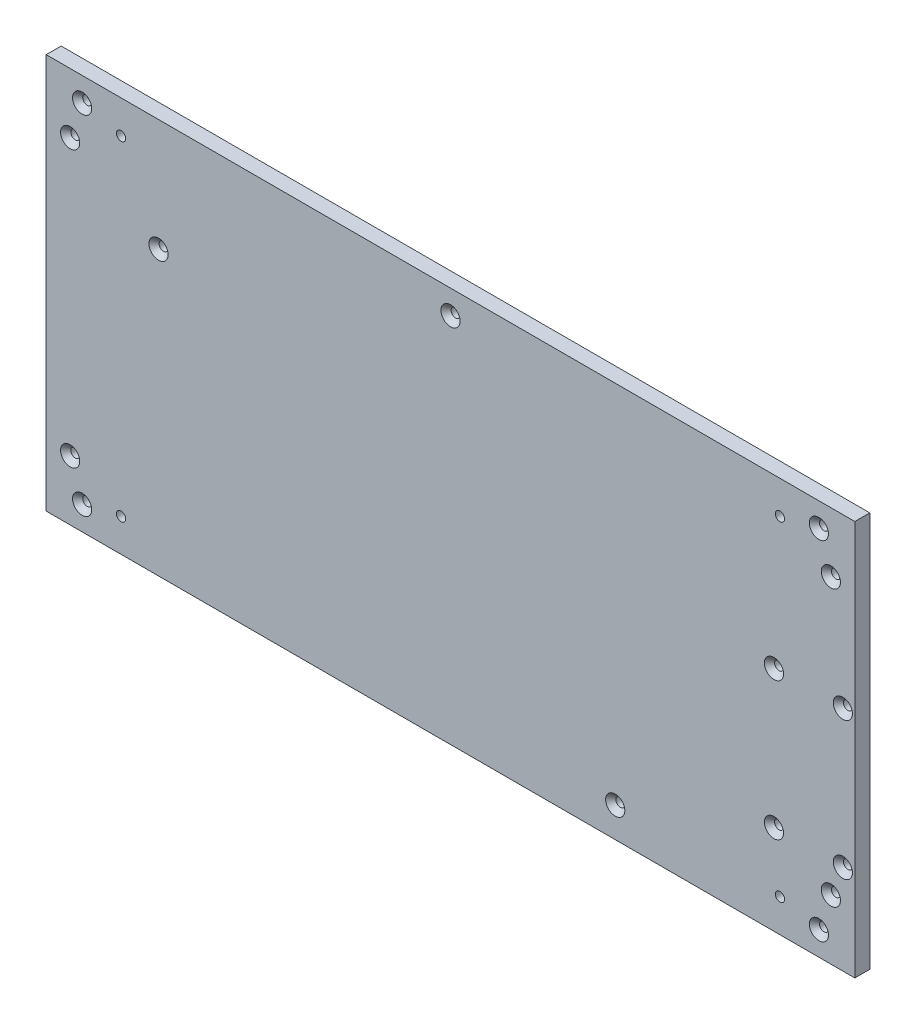
SolidWorks part; units mm, degrees
ref_plane "Front Plane" through (0, 0, 0) normal (0, 0, 1) x (1, 0, 0)
ref_plane "Top Plane" through (0, 0, 0) normal (0, 1, 0) x (1, 0, 0)
ref_plane "Right Plane" through (0, 0, 0) normal (1, 0, 0) x (0, 0, -1)
sketch "Sketch1" plane through (0, 0, 0) normal (0, 0, 1) x (1, 0, 0)
  line L1 (135, -66) -> (-135, -66)
  line L2 (135, -66) -> (135, 66)
  line L3 (135, 66) -> (-135, 66)
  line L4 (-135, -66) -> (-135, 66)
  line L5 (135, -66) -> (-135, 66) construction
  line L6 (135, 66) -> (-135, -66) construction
  point P0 (0, 0)
  dimension "D1" = 270
  dimension "D2" = 132
extrude "Base" add sketch "Sketch1" along normal mid plane 5 contours L4 L1 L2 L3 region at (0, 0, 0)
sketch "Sketch2" plane through (0, 0, 2.5) normal (0, 0, 1) x (1, 0, 0)
  line L0 (135, 66) -> (-135, 66) construction
  line L1 (135, -66) -> (135, 66) construction
  line L2 (-135, -66) -> (-135, 66) construction
  line L3 (135, -66) -> (-135, -66) construction
  circle A0 centre (-127, -46) radius 1.5
  circle A1 centre (-123, -58) radius 1.5
  circle A2 centre (-127, 46) radius 1.5
  circle A3 centre (-123, 58) radius 1.5
  circle A5 centre (0, 58) radius 1.5
  circle A6 centre (123, -58) radius 1.5
  circle A7 centre (127, -46) radius 1.5
  circle A8 centre (127, 46) radius 1.5
  circle A9 centre (123, 58) radius 1.5
  dimension "D5" = 8
  dimension "D10" = 3
  dimension "D2" = 8
  dimension "D3" = 12
  dimension "D4" = 12
  dimension "D6" = 20
  dimension "D7" = 20
  dimension "D8" = 8
  dimension "D9" = 8
extrude "FastenersHoles" cut sketch "Sketch2" against normal through all
sketch "Sketch3" plane through (0, 0, -2.5) normal (0, 0, -1) x (-1, 0, 0)
  line L1 (-135, -66) -> (135, -66) construction
  line L2 (-135, -66) -> (-135, 66) construction
  circle A0 centre (-55, -56) radius 1.5
  circle A1 centre (97.5, 28.5) radius 1.5
  dimension "D3" = 3
  dimension "D1" = 80
  dimension "D2" = 10
  dimension "D4" = 84.5
  dimension "D5" = 152.5
extrude "Cut-Extrude1" cut sketch "Sketch3" against normal through all
sketch "Sketch4" plane through (0, 0, 2.5) normal (0, 0, 1) x (1, 0, 0)
  line L1 (131, 10) -> (108, 10) construction
  line L2 (131, 10) -> (131, -36) construction
  line L3 (131, -36) -> (108, -36) construction
  line L4 (108, 10) -> (108, -36) construction
  line L5 (131, 10) -> (108, -36) construction
  line L6 (131, -36) -> (108, 10) construction
  line L7 (135, -66) -> (135, 66) construction
  circle A0 centre (108, 10) radius 1.5
  circle A1 centre (131, 10) radius 1.5
  circle A2 centre (108, -36) radius 1.5
  circle A3 centre (131, -36) radius 1.5
  point P0 (119.5, -13)
  point P16 (135, 0)
  dimension "D5" = 3
  dimension "D1" = 46
  dimension "D2" = 23
  dimension "D3" = 4
  dimension "D4" = 13
extrude "InterfaceHoles" cut sketch "Sketch4" against normal through all
chamfer "ChamferAll" distance 1.7 angle 45 15 edges at (53.5, -56, 2.5) (-121.5, -58, 2.5) (-125.5, -46, 2.5) (-121.5, 58, 2.5) (-125.5, 46, 2.5) (-99, 28.5, 2.5) (1.5, 58, 2.5) (124.5, 58, 2.5) (128.5, 46, 2.5) (128.5, -46, 2.5) (124.5, -58, 2.5) (132.5, 10, 2.5) (132.5, -36, 2.5) (109.5, -36, 2.5) (109.5, 10, 2.5)
sketch "Sketch5" plane through (0, 0, 2.5) normal (0, 0, 1) x (1, 0, 0)
  line L1 (110, -55) -> (-110, -55) construction
  line L2 (110, -55) -> (110, 55) construction
  line L3 (110, 55) -> (-110, 55) construction
  line L4 (-110, -55) -> (-110, 55) construction
  line L5 (110, -55) -> (-110, 55) construction
  line L6 (110, 55) -> (-110, -55) construction
  circle A0 centre (-110, -55) radius 1.55
  circle A1 centre (-110, 55) radius 1.55
  circle A2 centre (110, 55) radius 1.55
  circle A3 centre (110, -55) radius 1.55
  point P8 (0, 0)
  dimension "D1" = 3.1
  dimension "D2" = 110
  dimension "D3" = 220
extrude "Cut-Extrude2" cut sketch "Sketch5" against normal through all
